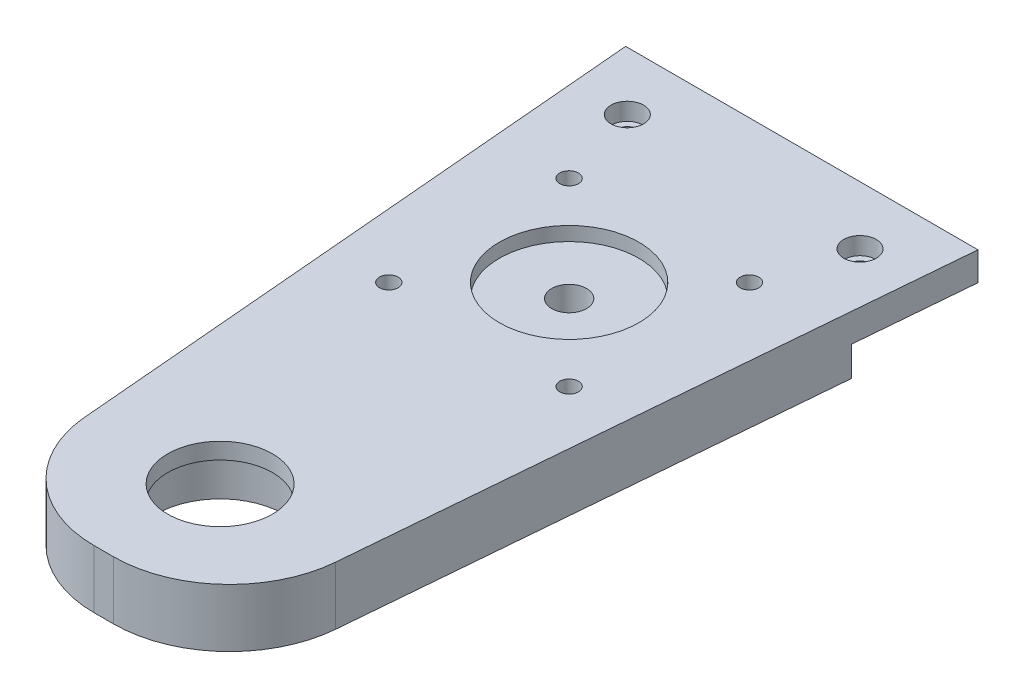
SolidWorks part; units mm, degrees
ref_plane "Front Plane" through (0, 0, 0) normal (0, 0, 1) x (1, 0, 0)
ref_plane "Top Plane" through (0, 0, 0) normal (0, 1, 0) x (1, 0, 0)
ref_plane "Right Plane" through (0, 0, 0) normal (1, 0, 0) x (0, 0, -1)
sketch "Sketch1" plane through (0, 0, 0) normal (0, 1, 0) x (1, 0, 0)
  circle A0 centre (0, 0) radius 50
extrude "Boss-Extrude1" add sketch "Sketch1" along normal blind 10
sketch "Sketch2" plane through (0, 10, 0) normal (0, 1, 0) x (1, 0, 0)
  circle A0 centre (0, 0) radius 20
extrude "Cut-Extrude1" cut sketch "Sketch2" against normal blind 5
sketch "Sketch7" plane through (0, 0, 0) normal (0, -1, 0) x (1, 0, 0)
  line L0 (10.1404, -5.8546) -> (10.1404, -9.1454)
  line L1 (0, 11.7091) -> (2.85, 13.3546)
  line L2 (2.85, 13.3546) -> (2.85, 16.6454)
  line L3 (2.85, 16.6454) -> (0, 18.2909)
  line L4 (0, 18.2909) -> (-2.85, 16.6454)
  line L5 (-2.85, 16.6454) -> (-2.85, 13.3546)
  line L6 (-2.85, 13.3546) -> (0, 11.7091)
  line L7 (10.1404, -9.1454) -> (12.9904, -10.7909)
  line L8 (12.9904, -10.7909) -> (15.8404, -9.1454)
  line L9 (15.8404, -9.1454) -> (15.8404, -5.8546)
  line L10 (15.8404, -5.8546) -> (12.9904, -4.2091)
  line L11 (12.9904, -4.2091) -> (10.1404, -5.8546)
  line L12 (-10.1404, -5.8546) -> (-12.9904, -4.2091)
  line L13 (-12.9904, -4.2091) -> (-15.8404, -5.8546)
  line L14 (-15.8404, -5.8546) -> (-15.8404, -9.1454)
  line L15 (-15.8404, -9.1454) -> (-12.9904, -10.7909)
  line L16 (-12.9904, -10.7909) -> (-10.1404, -9.1454)
  line L17 (-10.1404, -9.1454) -> (-10.1404, -5.8546)
  circle A0 centre (0, 0) radius 15
  circle A1 centre (0, 15) radius 2.85 construction
  point P25 (0, 0)
  dimension "D1" = 3
extrude "Cut-Extrude6" cut sketch "Sketch7" against normal blind 3 contours A0 L2 L3 L4 L5 | L2 A0 L5 L6 L1 | L13 L14 L15 L16 L17 L12 | L10 L11 L0 L7 L8 L9 region at (0, 0, 16.2315) region at (0, 0, 13.6745)
sketch "Sketch8" plane through (0, 0, 0) normal (0, -1, 0) x (1, 0, 0)
  line L0 (-2.85, 15) -> (2.85, 15) construction
  line L1 (-2.85, 16.6454) -> (-2.85, 13.3546) construction
  line L2 (2.85, 13.3546) -> (2.85, 16.6454) construction
  circle A0 centre (0, 15) radius 1.7
  circle A1 centre (12.9904, -7.5) radius 1.7
  circle A2 centre (-12.9904, -7.5) radius 1.7
  point P14 (0, 0)
  dimension "D1" = 3
extrude "Cut-Extrude7" cut sketch "Sketch8" against normal blind 10
sketch "Sketch9" plane through (0, 0, 0) normal (0, -1, 0) x (1, 0, 0)
  line L1 (-50, 0) -> (50, 0)
  line L2 (-50, 0) -> (-50, 350)
  line L3 (-50, 350) -> (50, 350)
  line L4 (50, 0) -> (50, 350)
  circle A0 centre (0, 0) radius 50 construction
  circle A1 centre (0, 0) radius 50
  circle M23 centre (0, 0) radius 50
  dimension "D1" = 350
extrude "Boss-Extrude3" add sketch "Sketch9" against normal blind 10 separate body contours L4 L3 L2 M23 region at (0, 0, 194.4346)
sketch "Sketch13" plane through (0, 0, 0) normal (0, -1, 0) x (1, 0, 0)
  line L0 (-50, 0) -> (-20, 350)
  line L1 (0, 350) -> (0, 0) construction
  line L2 (50, 0) -> (20, 350)
  line L3 (50, 0) -> (50, 350)
  line L4 (50, 350) -> (-50, 350)
  line L5 (-50, 350) -> (-50, 0)
  line L6 (50, 0) -> (50, 350)
  line L7 (50, 350) -> (-50, 350)
  line L8 (-50, 350) -> (-50, 0)
  arc A1 (50, 0) -> (-50, 0) centre (0, 0) ccw
  arc A2 (50, 0) -> (-50, 0) centre (0, 0) ccw
  arc M7 (-50, 0) -> (50, 0) centre (0, 0) cw
  line M8 (50, 0) -> (50, 350)
  line M9 (50, 350) -> (-50, 350)
  line M10 (-50, 350) -> (-50, 0)
  dimension "D2" = 20
  dimension "D1" = 0
extrude "Cut-Extrude11" cut sketch "Sketch13" against normal blind 10 contours L0 M7 M9 M10 | L2 M7 M8 M9 region at (-39.9981, 0, 233.3787) region at (39.9981, 0, 233.3787)
sketch "Sketch14" plane through (0, 0, 0) normal (0, -1, 0) x (1, 0, 0)
  line L0 (0, 0) -> (0, 125) construction
  line L2 (-64.1644, 125) -> (57.7014, 125)
  line L3 (-64.1644, 125) -> (-64.1644, 375)
  line L4 (-64.1644, 375) -> (57.7014, 375)
  line L5 (57.7014, 125) -> (57.7014, 375)
  dimension "D1" = 125
  dimension "D2" = 250
sketch "Sketch15" plane through (0, 10, 0) normal (0, 1, 0) x (1, 0, 0)
  line L1 (57.7014, -125) -> (-74.0337, -125)
  line L2 (57.7014, -125) -> (57.7014, 54.2666)
  line L3 (57.7014, 54.2666) -> (-74.0337, 54.2666)
  line L4 (-74.0337, -125) -> (-74.0337, 54.2666)
extrude "Cut-Extrude12" cut sketch "Sketch15" against normal blind 79
sketch "Sketch16" plane through (0, 10, 0) normal (0, 1, 0) x (1, 0, 0)
  line L0 (-40.9724, -105.3222) -> (-37.599, -144.6778)
  line L2 (-39.2857, -125) -> (-20, -350) construction
  line L3 (0, -125) -> (0, -150.7956) construction
  line L4 (40.9724, -105.3222) -> (37.599, -144.6778)
  line L5 (-40.9724, -105.3222) -> (40.9724, -105.3222)
  line L9 (20, -350) -> (39.2857, -125)
  line L10 (39.2857, -125) -> (-39.2857, -125)
  line L11 (-39.2857, -125) -> (-20, -350)
  line L12 (-20, -350) -> (20, -350)
  line L13 (20, -350) -> (39.2857, -125)
  line L14 (39.2857, -125) -> (-39.2857, -125)
  line L15 (-39.2857, -125) -> (-20, -350)
  line L16 (-20, -350) -> (20, -350)
  point P4 (-39.2857, -125)
  line M18 (39.2857, -125) -> (-39.2857, -125)
  dimension "D1" = 0
extrude "Boss-Extrude4" add sketch "Sketch16" against normal blind 4.9 contours L5 L0 L14 L4 M18 region at (0, 10, 115.0922)
sketch "Sketch17" plane through (0, 5.1, 0) normal (0, -1, 0) x (1, 0, 0)
  line L0 (0, 125) -> (0, 115) construction
  line L1 (0, 0) -> (0, 125) construction
  line L2 (-25, 115) -> (25, 115) construction
  circle A0 centre (-25, 115) radius 1.7
  circle A1 centre (25, 115) radius 1.7
  point P8 (0, 115)
extrude "Cut-Extrude13" cut sketch "Sketch17" against normal blind 10
sketch "Sketch18" plane through (0, 10, 0) normal (0, 1, 0) x (1, 0, 0)
  line L0 (0, -105.3222) -> (0, -125) construction
  line L1 (-25, -111.6514) -> (-27.9, -113.3257)
  line L2 (-27.9, -113.3257) -> (-27.9, -116.6743)
  line L3 (-27.9, -116.6743) -> (-25, -118.3486)
  line L4 (-25, -118.3486) -> (-22.1, -116.6743)
  line L5 (-22.1, -116.6743) -> (-22.1, -113.3257)
  line L6 (-22.1, -113.3257) -> (-25, -111.6514)
  line L7 (-40.9724, -105.3222) -> (40.9724, -105.3222) construction
  line L8 (22.1, -113.3257) -> (25, -111.6514)
  line L9 (22.1, -116.6743) -> (22.1, -113.3257)
  line L10 (25, -118.3486) -> (22.1, -116.6743)
  line L11 (27.9, -116.6743) -> (25, -118.3486)
  line L12 (27.9, -113.3257) -> (27.9, -116.6743)
  line L13 (25, -111.6514) -> (27.9, -113.3257)
  circle A0 centre (-25, -115) radius 2.9 construction
  circle A1 centre (25, -115) radius 2.9 construction
extrude "Cut-Extrude14" cut sketch "Sketch18" against normal blind 3
sketch "Sketch19" plane through (0, 0, 125) normal (0, 0, -1) x (-1, 0, 0)
  line L4 (39.2857, 5.1) -> (-39.2857, 5.1)
  line L5 (-39.2857, 5.1) -> (-39.2857, 0)
  line L6 (-39.2857, 0) -> (39.2857, 0)
  line L7 (39.2857, 0) -> (39.2857, 5.1)
  line L8 (39.2857, 5.1) -> (-39.2857, 5.1)
  line L9 (-39.2857, 5.1) -> (-39.2857, 0)
  line L10 (-39.2857, 0) -> (39.2857, 0)
  line L11 (39.2857, 0) -> (39.2857, 5.1)
  dimension "D1" = 0
extrude "Cut-Extrude15" cut sketch "Sketch19" against normal blind 0.5
sketch "Sketch20" plane through (0, 0, 0) normal (0, -1, 0) x (1, 0, 0)
  line L0 (-20, 350) -> (20, 350) construction
  line L1 (-45.6201, 364.5287) -> (46.9916, 364.5287)
  line L2 (-45.6201, 364.5287) -> (-45.6201, 250)
  line L3 (-45.6201, 250) -> (46.9916, 250)
  line L4 (46.9916, 364.5287) -> (46.9916, 250)
  dimension "D1" = 100
sketch "Sketch21" plane through (0, 0, 0) normal (0, -1, 0) x (1, 0, 0)
  line L0 (-45.6201, 230) -> (46.4959, 230)
  line L1 (-45.6201, 250) -> (46.4959, 250)
  line L2 (-45.6201, 250) -> (-45.6201, 89.1126)
  line L3 (-45.6201, 89.1126) -> (46.4959, 89.1126)
  line L4 (46.4959, 250) -> (46.4959, 89.1126)
  line M10 (-20, 350) -> (-39.2429, 125.5)
  line M11 (-39.2429, 125.5) -> (39.2429, 125.5)
  line M12 (39.2429, 125.5) -> (20, 350)
  dimension "D1" = 20
extrude "Cut-Extrude16" cut sketch "Sketch21" against normal blind 10 contours L0 M10 M11 M12 | L4 L0 L2 L3 M12 M11 M10 region at (-37.9529, 0, 228.3167) region at (0, 0, 175.5063)
extrude "Cut-Extrude17" cut sketch "Sketch21<3>" against normal blind 5.1 contours L1 L0 M10 M12 region at (0, 0, 239.9029)
sketch "Sketch21<3>" plane through (0, 0, 0) normal (0, -1, 0) x (1, 0, 0) same geometry as "Sketch21"
sketch "Sketch24" plane through (0, 5.1, 0) normal (0, -1, 0) x (1, 0, 0)
  line L0 (-28.5714, 250) -> (28.5714, 250) construction
  line L1 (0, 250) -> (0, 230) construction
  line L2 (-30.2857, 230) -> (30.2857, 230) construction
  line L3 (-20, 240) -> (20, 240) construction
  circle A0 centre (20, 240) radius 1.7
  circle A1 centre (-20, 240) radius 1.7
  point P11 (0, 240)
  dimension "D1" = 40
extrude "Cut-Extrude19" cut sketch "Sketch24" against normal blind 5.1
sketch "Sketch25" plane through (0, 0, 0) normal (0, -1, 0) x (1, 0, 0)
  line L0 (0, 350) -> (0, 330) construction
  line L1 (-20, 350) -> (20, 350) construction
  circle A0 centre (0, 330) radius 11
  dimension "D1" = 22
extrude "Cut-Extrude20" cut sketch "Sketch25" against normal blind 7.2 contours A0
sketch "Sketch26" plane through (0, 7.2, 0) normal (0, -1, 0) x (1, 0, 0)
  circle A0 centre (0, 330) radius 9
  dimension "D1" = 18
extrude "Cut-Extrude21" cut sketch "Sketch26" against normal blind 7.2
sketch "Sketch27" plane through (0, 0, 0) normal (0, -1, 0) x (1, 0, 0)
  line L0 (0, 330) -> (0, 270) construction
  circle A0 centre (0, 270) radius 3
  dimension "D2" = 6
  dimension "D1" = 60
extrude "Cut-Extrude22" cut sketch "Sketch27" against normal blind 11
sketch "Sketch28" plane through (0, 10, 0) normal (0, 1, 0) x (1, 0, 0)
  line L1 (-15.5, -254.5) -> (15.5, -254.5)
  line L2 (-15.5, -254.5) -> (-15.5, -285.5)
  line L3 (-15.5, -285.5) -> (15.5, -285.5)
  line L4 (15.5, -254.5) -> (15.5, -285.5)
  line L5 (-15.5, -254.5) -> (15.5, -285.5) construction
  line L6 (-15.5, -285.5) -> (15.5, -254.5) construction
  circle A0 centre (-15.5, -254.5) radius 1.6
  circle A1 centre (15.5, -254.5) radius 1.6
  circle A2 centre (15.5, -285.5) radius 1.6
  circle A3 centre (-15.5, -285.5) radius 1.6
  point P0 (0, -270)
  point P16 (0, -270)
  dimension "D3" = 4
  dimension "D1" = 31
  dimension "D2" = 31
extrude "Cut-Extrude23" cut sketch "Sketch28" against normal blind 12 contours A1 | A0 | A3 | A2
sketch "Sketch29" plane through (0, 0, 0) normal (0, -1, 0) x (1, 0, 0)
  circle A0 centre (-15.5, 285.5) radius 1.6 construction
  circle A1 centre (-15.5, 285.5) radius 1.6
  circle A2 centre (-15.5, 285.5) radius 2.9
  circle A3 centre (15.5, 285.5) radius 2.9
  circle A4 centre (15.5, 254.5) radius 2.9
  circle A5 centre (-15.5, 254.5) radius 2.9
  point P14 (0, 270)
  dimension "D1" = 1.3
  dimension "D2" = 4
extrude "Cut-Extrude24" cut sketch "Sketch29" against normal blind 3.5
sketch "Sketch30" plane through (0, 10, 0) normal (0, 1, 0) x (1, 0, 0)
  circle A0 centre (0, -270) radius 12
  dimension "D1" = 24
extrude "Cut-Extrude25" cut sketch "Sketch30" against normal blind 2.4
sketch "Sketch31" plane through (0, 10, 0) normal (0, 1, 0) x (1, 0, 0)
  circle A0 centre (-20, -240) radius 2.8
  circle A1 centre (20, -240) radius 2.8
  dimension "D1" = 5.6
  dimension "D2" = 5.6
extrude "Cut-Extrude26" cut sketch "Sketch31" against normal blind 3
fillet "Fillet1" radius 20 2 edges at (-20, 5, 350) (20, 5, 350)
